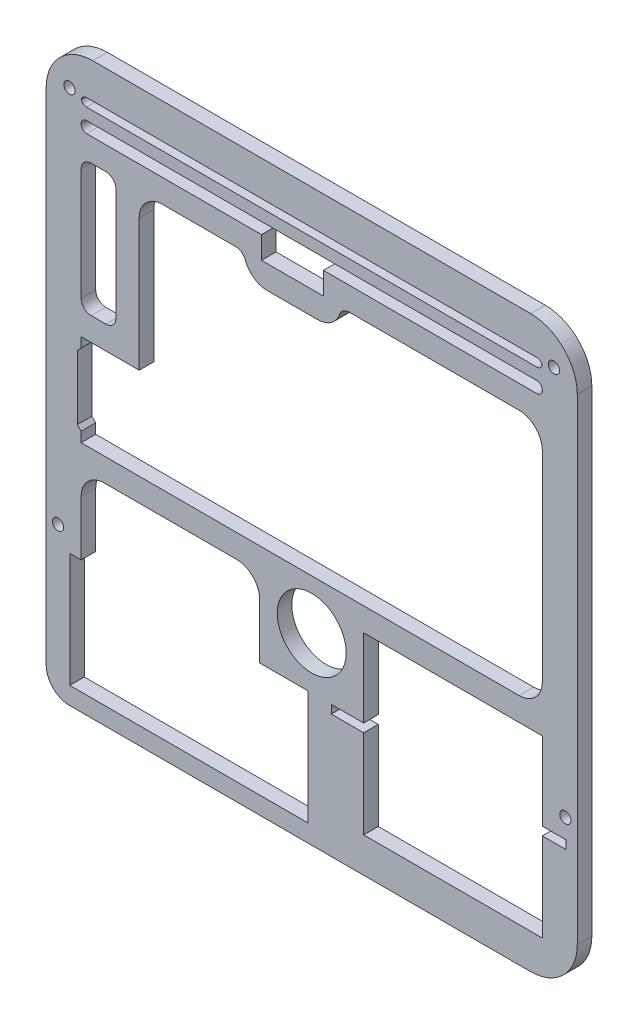
SolidWorks part; units mm, degrees
ref_plane "Front Plane" through (0, 0, 0) normal (0, 0, 1) x (1, 0, 0)
ref_plane "Top Plane" through (0, 0, 0) normal (0, 1, 0) x (1, 0, 0)
ref_plane "Right Plane" through (0, 0, 0) normal (1, 0, 0) x (0, 0, -1)
sketch "Sketch1" plane through (0, 0, 0) normal (0, 0, 1) x (1, 0, 0)
  line L0 (63.9883, 52.5442) -> (63.9883, 48.7342) construction
  line L1 (6.1648, -9.556) -> (64.0322, -9.556)
  line L2 (6.1648, -9.556) -> (6.1648, 52.5442)
  line L3 (6.1648, 52.5442) -> (64.0322, 52.5442)
  line L4 (64.0322, -9.556) -> (64.0322, 52.5442)
  line L5 (60.2222, 48.7342) -> (9.9748, 48.7342)
  line L6 (60.2222, 48.7342) -> (60.2222, -5.746)
  line L7 (60.2222, -5.746) -> (9.9748, -5.746)
  line L8 (9.9748, 48.7342) -> (9.9748, -5.746)
  line L9 (63.9883, 50.6392) -> (18.0707, 50.6392) construction
  line L10 (9.9748, 39.3805) -> (6.1648, 39.3805) construction
  line L11 (8.0698, 39.3805) -> (8.0698, 23.9527) construction
  line L12 (13.5248, -5.746) -> (13.5248, -9.556) construction
  line L13 (13.5248, -7.651) -> (21.1598, -7.651) construction
  line L14 (64.0322, 38.1916) -> (60.2222, 38.1916) construction
  line L15 (62.1272, 38.1916) -> (62.1272, 22.3321) construction
  line L16 (48.6748, 50.6392) -> (23.5288, 50.6392) construction
  line L17 (62.1272, 27.1202) -> (62.1272, 39.363) construction
  line L18 (8.0698, 15.868) -> (8.0698, 3.6252) construction
  line L19 (35.2238, -7.651) -> (34.6952, -7.651) construction
  dimension "D1" = 3.81
  dimension "D2" = 3.81
extrude "Boss-Extrude1" add sketch "Sketch1" along normal blind 1.5875
sketch "Sketch2" plane through (0, 0, 0) normal (0, 0, -1) x (-1, 0, 0)
  line L0 (-60.2222, -5.746) -> (-60.2222, 48.7342) construction
  line L1 (-60.2222, 15.868) -> (-9.9748, 15.868)
  line L2 (-60.2222, 15.868) -> (-60.2222, 13.328)
  line L3 (-60.2222, 13.328) -> (-9.9748, 13.328)
  line L4 (-9.9748, 15.868) -> (-9.9748, 13.328)
  line L5 (-9.9748, 48.7342) -> (-9.9748, -5.746) construction
  line L6 (-13.0532, 15.868) -> (-50.7532, 15.868) construction
  line L7 (-36.3812, 45.3306) -> (-36.3812, 43.2224) construction
  line L8 (-29.6248, 43.2224) -> (-29.6248, 45.3306) construction
  line L9 (-25.4592, 42.9049) -> (-46.8968, 42.9049) construction
  line L11 (-60.2222, 45.3306) -> (-36.3812, 45.3306)
  line L12 (-60.2222, 45.3306) -> (-60.2222, 42.7906)
  line L13 (-60.2222, 42.7906) -> (-38.2862, 42.7906)
  line L14 (-9.9748, 45.3306) -> (-9.9748, 42.7906)
  line L15 (-60.2222, 47.8325) -> (-9.9748, 47.8325)
  line L16 (-60.2222, 47.8325) -> (-60.2222, 46.5625)
  line L17 (-60.2222, 46.5625) -> (-9.9748, 46.5625)
  line L18 (-9.9748, 47.8325) -> (-9.9748, 46.5625)
  line L20 (-55.2788, 45.3306) -> (-16.9248, 45.3306) construction
  line L21 (-55.2788, 46.5625) -> (-16.9248, 46.5625) construction
  line L22 (-36.3812, 42.9049) -> (-36.3812, 45.3306)
  line L23 (-29.6248, 42.9049) -> (-36.3812, 42.9049)
  line L24 (-29.6248, 42.9049) -> (-29.6248, 45.3306)
  line L25 (-38.2862, 42.7906) -> (-38.2862, 40.3649)
  line L26 (-38.2862, 40.3649) -> (-27.7198, 40.3649)
  line L27 (-27.7198, 40.3649) -> (-27.7198, 42.7906)
  line L28 (-27.7198, 42.7906) -> (-9.9748, 42.7906)
  line L29 (-29.6248, 45.3306) -> (-9.9748, 45.3306)
  dimension "D1" = 2.54
  dimension "D2" = 1.905
  dimension "D3" = 2.54
  dimension "D4" = 1.905
  dimension "D5" = 1.27
extrude "Boss-Extrude2" add sketch "Sketch2" against normal up to surface (1.5875 mm away) up to face at (35.0985, 21.4941, 1.5875)
sketch "Sketch3" plane through (0, 0, 0) normal (0, 0, -1) x (-1, 0, 0)
  line L11 (-16.3032, 25.868) -> (-13.0532, 25.868) construction
  line L12 (-16.3032, 25.868) -> (-13.0532, 25.868)
  line L13 (-13.0532, 25.868) -> (-9.9748, 25.868)
  line L14 (-9.9748, 42.7906) -> (-9.9748, 15.868) construction
  line L15 (-9.9748, 25.868) -> (-9.9748, 28.408)
  line L16 (-9.9748, 28.408) -> (-13.7632, 28.408)
  line L17 (-13.7632, 28.408) -> (-13.7632, 42.7906)
  line L18 (-27.7198, 42.7906) -> (-9.9748, 42.7906) construction
  line L19 (-13.7632, 42.7906) -> (-16.3032, 42.7906)
  line L20 (-16.3032, 42.7906) -> (-16.3032, 25.868)
  line L21 (-16.3032, 25.868) -> (-16.2412, 25.8471)
  line M27 (-27.7198, 42.7906) -> (-9.9748, 42.7906)
  line M28 (-9.9748, 42.7906) -> (-9.9748, 15.868)
  dimension "D3" = 2.54
  dimension "D4" = 2.54
extrude "Boss-Extrude3" add sketch "Sketch3" against normal up to surface (1.5875 mm away) contours L20 L12 L13 L16 L17 M27 M28 region at (14.4544, 33.0139, 0) up to face at (35.0985, 48.2834, 1.5875)
sketch "Sketch4" plane through (0, 0, 0) normal (0, 0, -1) x (-1, 0, 0)
  line L0 (-60.2222, 13.328) -> (-9.9748, 13.328) construction
  line L1 (-40.7627, 13.328) -> (-29.4343, 13.328)
  line L2 (-40.7627, 13.328) -> (-40.7627, -5.746)
  line L3 (-40.7627, -5.746) -> (-29.4343, -5.746)
  line L4 (-29.4343, 13.328) -> (-29.4343, -5.746)
  line L5 (-9.9748, -5.746) -> (-60.2222, -5.746) construction
  line L6 (-38.8577, 10.4578) -> (-40.7627, 10.4578) construction
  line L7 (-31.3393, 10.4578) -> (-29.4343, 10.4578) construction
  circle A0 centre (-35.0985, 10.4578) radius 3.7592 construction
  dimension "D1" = 1.905
extrude "Boss-Extrude4" add sketch "Sketch4" against normal up to surface (1.5875 mm away) up to face at (11.869, 35.5993, 1.5875)
sketch "Sketch5" plane through (0, 0, 0) normal (0, 0, -1) x (-1, 0, 0)
  line L0 (-8.7364, 4.8077) -> (-34.6952, 4.8077) construction
  line L3 (-34.6952, -7.651) -> (-34.6952, 4.8077) construction
  line L4 (-8.7364, -7.651) -> (-34.6952, -7.651) construction
  line L5 (-8.7364, -7.651) -> (-8.7364, 4.8077) construction
  line L6 (-8.7364, 4.8077) -> (-34.6952, 4.8077)
  line L7 (-34.6952, -7.651) -> (-34.6952, 4.8077)
  line L8 (-8.7364, -7.651) -> (-34.6952, -7.651)
  line L9 (-8.7364, -7.651) -> (-8.7364, 4.8077)
  circle A0 centre (-35.0985, 10.4578) radius 3.7592 construction
  circle A1 centre (-35.0985, 10.4578) radius 3.7592
extrude "Cut-Extrude1" cut sketch "Sketch5" against normal up to surface (1.5875 mm away) up to face at (50.4924, 3.791, 1.5875)
fillet "Fillet1" radius 5.08 3 edges at (64.0322, -9.556, 0.7937) (6.1648, 52.5442, 0.7937) (64.0322, 52.5442, 0.7937)
fillet "Fillet2" radius 2.54 7 edges at (16.3032, 42.7906, 0.7937) (27.7198, 40.3649, 0.7937) (60.2222, 42.7906, 0.7937) (60.2222, 15.868, 0.7937) (9.9748, 13.328, 0.7937) (29.4343, 13.328, 0.7937) (38.2862, 40.3649, 0.7937)
fillet "Fillet3" radius 1.0922 6 edges at (9.9748, 28.408, 0.7937) (13.7632, 28.408, 0.7937) (9.9748, 42.7906, 0.7937) (13.7632, 42.7906, 0.7937) (27.7198, 42.7906, 0.7937) (38.2862, 42.7906, 0.7937)
fillet "Fillet4" radius 0.5842 8 edges at (9.9748, 45.3306, 0.7937) (9.9748, 47.8325, 0.7937) (9.9748, 48.7342, 0.7937) (9.9748, 46.5625, 0.7937) (60.2222, 47.8325, 0.7937) (60.2222, 48.7342, 0.7937) (60.2222, 46.5625, 0.7937) (60.2222, 45.3306, 0.7937)
fillet "Fillet5" radius 2.54 1 edges at (6.1648, -9.556, 0.7937)
sketch "Sketch6" plane through (0, 0, 0) normal (0, 0, -1) x (-1, 0, 0)
  line L0 (-9.5532, 24.368) -> (-9.5532, 17.368) construction
  line L1 (-9.5532, 24.368) -> (-9.5532, 17.368)
  line L2 (-11.0532, 25.868) -> (-9.5532, 24.368) construction
  line L3 (-11.0532, 25.868) -> (-9.5532, 24.368)
  line L4 (-11.0532, 25.868) -> (-11.0532, 15.868)
  line L6 (-13.0532, 17.368) -> (-13.0532, 15.868)
  line L7 (-13.0532, 15.868) -> (-11.0532, 15.868)
  line L8 (-11.0532, 15.868) -> (-9.5532, 17.368)
  line L9 (-9.5532, 17.368) -> (-13.0532, 17.368)
  line L12 (-11.0532, 15.868) -> (-9.5532, 17.368)
  circle A0 centre (-61.4922, 48.7342) radius 0.6096 construction
  circle A1 centre (-8.7048, 48.7342) radius 0.6096 construction
  circle A2 centre (-62.7368, 6.9018) radius 0.6096 construction
  circle A3 centre (-7.4602, 6.9018) radius 0.6096 construction
  circle A4 centre (-61.4922, 48.7342) radius 0.6096
  circle A5 centre (-8.7048, 48.7342) radius 0.6096
  circle A6 centre (-62.7368, 6.9018) radius 0.6096
  circle A7 centre (-7.4602, 6.9018) radius 0.6096
  dimension "D1" = 0
extrude "Cut-Extrude2" cut sketch "Sketch6" against normal up to surface (1.5875 mm away) up to face at (31.3393, 10.4578, 1.5875)
sketch "Sketch9" plane through (0, 0, 1.5875) normal (0, 0, 1) x (1, 0, 0)
  line L4 (62.813, 4.8077) -> (37.2352, 4.8077)
  line L5 (37.2352, 4.8077) -> (37.2352, 3.8933)
  line L6 (37.2352, 3.8933) -> (62.813, 3.8933)
  line L7 (62.813, 3.8933) -> (62.813, 4.8077)
  line L8 (62.813, 4.8077) -> (37.2352, 4.8077)
  line L9 (37.2352, 4.8077) -> (37.2352, 3.8933)
  line L10 (37.2352, 3.8933) -> (62.813, 3.8933)
  line L11 (62.813, 3.8933) -> (62.813, 4.8077)
  dimension "D1" = 0
extrude "Cut-Extrude3" cut sketch "Sketch9" against normal up to surface (1.5875 mm away) up to face at (28.6741, 31.6821, 0)
